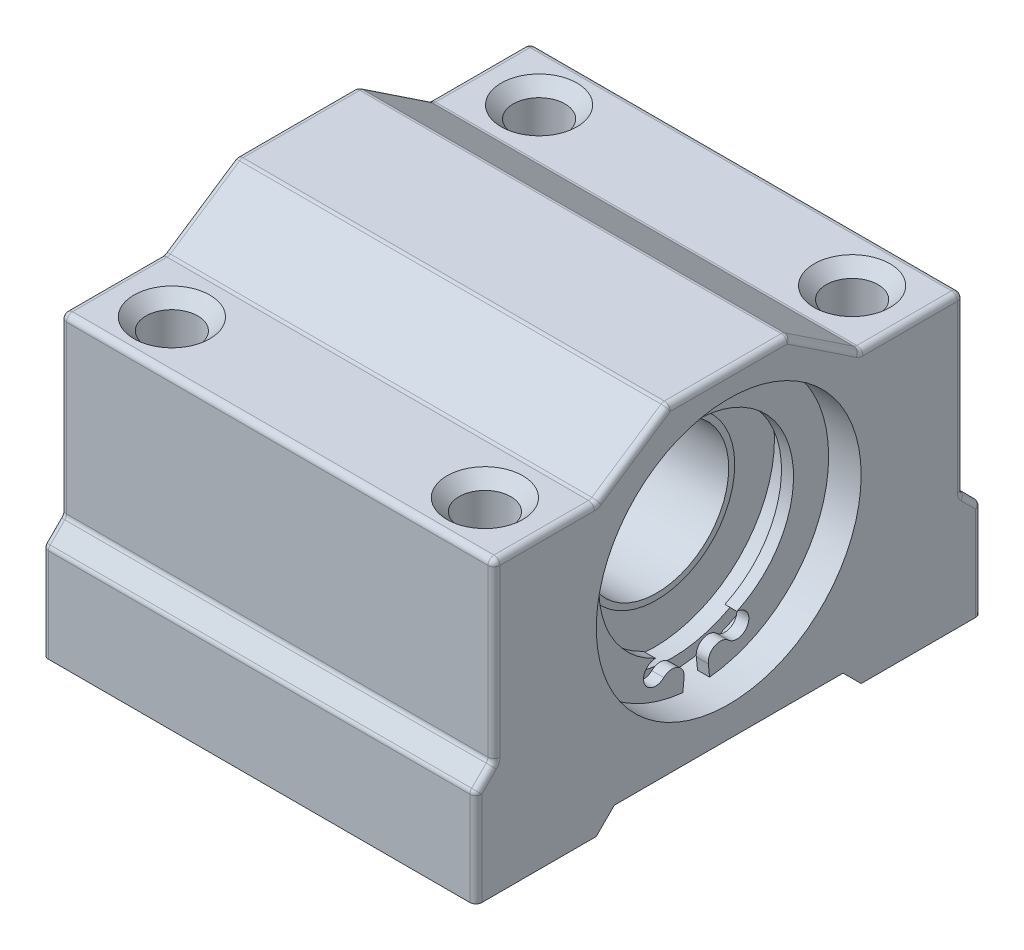
SolidWorks part; units mm, degrees
ref_plane "Front Plane" through (0, 0, 0) normal (0, 0, 1) x (1, 0, 0)
ref_plane "Top Plane" through (0, 0, 0) normal (0, 1, 0) x (1, 0, 0)
ref_plane "Right Plane" through (0, 0, 0) normal (1, 0, 0) x (0, 0, -1)
sketch "Sketch1" plane through (0, 0, 0) normal (1, 0, 0) x (0, 0, -1)
  line L1 (-11, -15) -> (-9.5, -13.5)
  line L2 (-9.5, -13.5) -> (9.5, -13.5)
  line L3 (9.5, -13.5) -> (11, -15)
  line L4 (11, -15) -> (21, -15)
  line L6 (21, -7) -> (19.5, -5.5)
  line L8 (19.5, 9) -> (11, 9)
  line L9 (11, 9) -> (5, 13)
  line L10 (5, 13) -> (-5, 13)
  line L11 (-5, 13) -> (-11, 9)
  line L12 (-11, 9) -> (-19.5, 9)
  line L15 (-21, -7) -> (-21, -15)
  line L16 (0, -13.5) -> (0, 13) construction
  line L17 (-16.278, 0) -> (14.0247, 0) construction
  line L18 (-21, -15) -> (-11, -15)
  line L19 (21, -7) -> (21, -15)
  line L20 (-19.5, -5.5) -> (-19.5, 9)
  line L21 (19.5, -5.5) -> (19.5, 9)
  line L22 (-15.25, 9) -> (-15.25, -15) construction
  line L23 (-15.25, -15) -> (15.25, 9) construction
  line L24 (15.25, 9) -> (15.25, -15) construction
  line L25 (-21, -7) -> (-19.5, -5.5)
  line L26 (-11, 0) -> (11, 0) construction
  circle A0 centre (0, 0) radius 11
  circle A1 centre (0, 0) radius 10
  circle A2 centre (0, 0) radius 6
  point P18 (0, 13)
  dimension "D12" = 12
  dimension "D1" = 42
  dimension "D2" = 24
  dimension "D3" = 15
  dimension "D5" = 28
  dimension "D6" = 30.5
  dimension "D4" = 8
  dimension "D7" = 1.5
  dimension "D8" = 10
  dimension "D9" = 1.5
  dimension "D10" = 10
  dimension "D11" = 1
extrude "Boss-Extrude1" add sketch "Sketch1" along normal blind 36 contours L25 L15 L18 L1 L2 L3 L4 L19 L6 L21 L8 L9 L10 L11 L12 L20 A0 region at (0, -14.4952, 16)
extrude "Extrude-Thin1" add sketch "Sketch1<4>" along normal blind 29.5 from offset 0.5 separate body thin contours A2 thin type one direction wall 0.5
sketch "Sketch1<4>" plane through (0, 0, 0) normal (1, 0, 0) x (0, 0, -1) same geometry as "Sketch1"
extrude "Boss-Extrude2" add sketch "Sketch1<5>" along normal blind 29 from offset 0.8 contours A1 A2 region at (0, 0, 9.7172)
sketch "Sketch1<5>" plane through (0, 0, 0) normal (1, 0, 0) x (0, 0, -1) same geometry as "Sketch1"
extrude "Boss-Extrude3" add sketch "Sketch1<6>" along normal blind 31 from offset 0.3 contours A0 A1 region at (0, 0, 10.6889)
sketch "Sketch1<6>" plane through (0, 0, 0) normal (1, 0, 0) x (0, 0, -1) same geometry as "Sketch1"
ref_plane "Plane1" through (31.3, 0, 0) normal (1, 0, 0) x (0, 0, -1)
sketch "Sketch3" plane through (31.3, 0, 0) normal (1, 0, 0) x (0, 0, -1)
  line L0 (0, 0) -> (0, -50000) construction
  line L1 (-1.0114, -9.9487) -> (-1.1126, -10.9436)
  line L2 (1.0114, -9.9487) -> (1.1126, -10.9436)
  circle A0 centre (0, 0) radius 11 construction
  arc A1 (1.1126, -10.9436) -> (-1.1126, -10.9436) centre (0, 0) ccw
  circle A2 centre (0, 0) radius 10 construction
  arc A3 (0, -10) -> (1.0114, -9.9487) centre (0, 0) ccw
  arc A4 (-1.0114, -9.9487) -> (-2.6866, -9.0709) centre (-2, -9.798) ccw
  circle A5 centre (-2, -9.798) radius 0.25
  arc A6 (-2.2443, -9.7449) -> (-1.7544, -9.8449) centre (0, 0) ccw
  arc A7 (-2.6866, -9.0709) -> (-3.3785, -7.3439) centre (-3.3732, -8.3439) cw
  arc A8 (2.6866, -9.0709) -> (3.3785, -7.3439) centre (3.3732, -8.3439) ccw
  circle A10 centre (2, -9.798) radius 0.25
  arc A11 (1.0114, -9.9487) -> (2.6866, -9.0709) centre (2, -9.798) cw
  arc A13 (3.3785, -7.3439) -> (-3.3785, -7.3439) centre (0, 0) ccw
  dimension "D1" = 0.5
  dimension "D2" = 2
  dimension "D3" = 1
  dimension "D4" = 2
extrude "Boss-Extrude4" add sketch "Sketch3" along normal blind 1 from offset 1 contours A11 A8 A13 A7 A4 L1 A1 L2
fillet "Fillet1" radius 0.5 32 edges at (18, -5.5, -19.5) (18, -5.5, 19.5) (18, -7, 21) (18, -7, -21) (18, 9, -11) (18, 9, 11) (18, 13, 5) (18, 13, -5) (18, 9, -19.5) (18, 9, 19.5) (36, 11, -8) (36, 11, 8) (36, 1.75, 19.5) (0, -6.25, 20.25) (0, 11, 8) (36, -6.25, -20.25) (36, -11, -21) (36, 1.75, -19.5) (36, 13, 0) (36, 9, -15.25) (36, 9, 15.25) (36, -6.25, 20.25) (36, -11, 21) (0, -11, -21) (0, -6.25, -20.25) (0, 1.75, -19.5) (0, 11, -8) (0, 9, -15.25) (0, 13, 0) (0, -11, 21) (0, 1.75, 19.5) (0, 9, 15.25)
sketch "Sketch4" plane through (0, -15, 0) normal (0, -1, 0) x (1, 0, 0)
  line L0 (18, 21) -> (18, -21) construction
  line L1 (35.5, 21) -> (0.5, 21) construction
  line L2 (35.5, -21) -> (0.5, -21) construction
  line L4 (-4.9444, 15.25) -> (27.0918, 15.25) construction
  line L6 (0, 0) -> (36.1646, 0) construction
  circle A0 centre (5, 15.25) radius 2.15
  circle A1 centre (31, 15.25) radius 2.15
  circle A2 centre (31, -15.25) radius 2.15
  circle A3 centre (5, -15.25) radius 2.15
  dimension "D2" = 4.3
  dimension "D1" = 15.25
  dimension "D3" = 26
extrude "Cut-Extrude3" cut sketch "Sketch4" against normal through all
chamfer "Chamfer1" distance 1 angle 45 6 edges at (31, 9, -17.4) (5, 9, -17.4) (5, 9, 13.1) (31, 9, 13.1) (31, -15, 17.4) (5, -15, 13.1)
equation "\"D1@Boss-Extrude2\"= \"D1@Boss-Extrude1\" - 2 - 5"
equation "\"D1@Boss-Extrude3\"= \"D1@Boss-Extrude1\" - 5"
equation "\"D1@Sketch4\"= \"D6@Sketch1\" / 2"
equation "\"D1@Extrude-Thin1\"= \"D1@Boss-Extrude3\" - 1.5"
